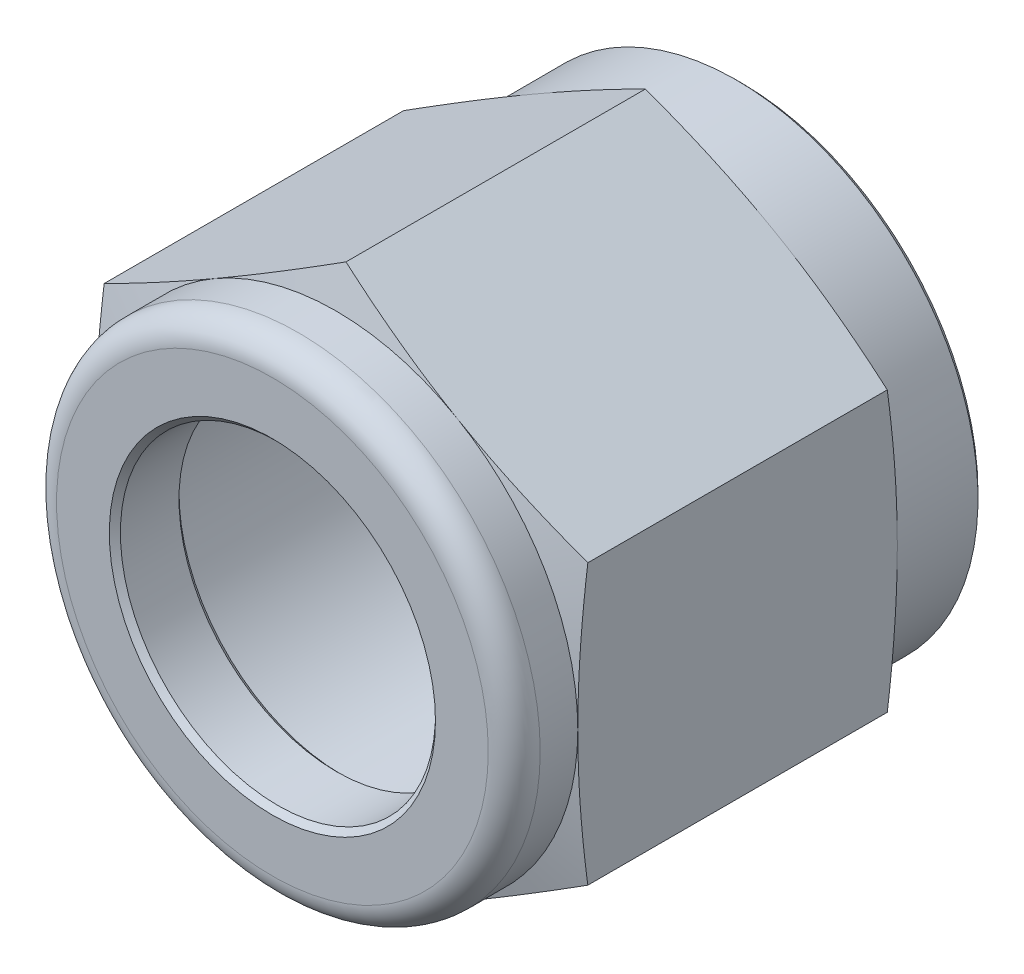
SolidWorks part; units mm, degrees
material "2024 Alloy"
ref_plane "Front Plane" through (0, 0, 0) normal (0, 0, 1) x (1, 0, 0)
ref_plane "Top Plane" through (0, 0, 0) normal (0, 1, 0) x (1, 0, 0)
ref_plane "Right Plane" through (0, 0, 0) normal (1, 0, 0) x (0, 0, -1)
sketch "Sketch0" plane through (0, 0, 0) normal (1, 0, 0) x (0, 0, -1)
  line L0 (0, 0) -> (-21.5646, 0) construction
  line L4 (-21.5646, 11.1125) -> (-21.5646, -11.1125) construction
  line L5 (-21.5646, 11.1125) -> (-21.5646, -11.1125) construction
  line L6 (-21.5646, 7.239) -> (-21.5646, -7.239) construction
  line L7 (0, 9.525) -> (0, -9.525) construction
  line L8 (0, -9.525) -> (0, 9.525) construction
  line L9 (0, -9.525) -> (-1.5875, -9.525) construction
  point P16 (-18.3642, 0)
  point P20 (-16.4338, 0)
  point P22 (-12.2936, 0)
  point P34 (-3.9624, 0)
  point P35 (-18.6436, 0)
  dimension "P" = 22.225
  dimension "M" = 21.5646
  dimension "L" = 18.3642
  dimension "S" = 16.4338
  dimension "Q" = 12.2936
  dimension "A" = 14.478
  dimension "C" = 22.225
  dimension "T" = 19.05
  dimension "B" = 3.9624
  dimension "J" = 14.6812
  dimension "H" = 19.05
  dimension "Pitch" = 1.5875
sketch "Sketch1" plane through (0, 0, 0) normal (0, 0, 1) x (1, 0, 0)
  line L1 (0, 12.8316) -> (-11.1125, 6.4158)
  line L2 (-11.1125, 6.4158) -> (-11.1125, -6.4158)
  line L3 (-11.1125, -6.4158) -> (0, -12.8316)
  line L4 (0, -12.8316) -> (11.1125, -6.4158)
  line L5 (11.1125, -6.4158) -> (11.1125, 6.4158)
  line L6 (11.1125, 6.4158) -> (0, 12.8316)
  circle A0 centre (0, 0) radius 11.1125 construction
extrude "Boss-Extrude1" add sketch "Sketch1" along normal up to vertex (21.5646 mm away) up to point (0, 0, 21.5646)
sketch "Sketch2" plane through (0, 0, 0) normal (1, 0, 0) x (0, 0, -1)
  line L0 (-21.5646, 14.5507) -> (-21.5646, 11.1125)
  line L1 (-21.5646, 11.1125) -> (-18.6436, 11.1125)
  line L2 (-18.6436, 11.1125) -> (-18.183, 12.8316)
  line L3 (-21.5646, 12.8316) -> (0, 12.8316) construction
  line L4 (-18.183, 12.8316) -> (-4.423, 12.8316)
  line L5 (-4.423, 12.8316) -> (-3.9624, 11.1125)
  line L6 (-3.9624, 11.1125) -> (-18.6436, 11.1125) construction
  line L7 (-3.9624, 11.1125) -> (0, 11.1125)
  line L8 (0, 11.1125) -> (0, 14.5507)
  line L9 (-21.5646, 14.5507) -> (0, 14.5507)
  line L10 (-3.9624, 11.1125) -> (-3.9624, 0) construction
  line L11 (-18.6436, 11.1125) -> (-18.6436, 0) construction
  line L12 (-21.5646, 7.239) -> (-21.5646, 0)
  line L13 (-21.5646, 11.1125) -> (-21.5646, -11.1125) construction
  line L14 (-21.5646, 0) -> (0, 0)
  line L15 (0, 0) -> (0, 8.7517)
  line L16 (-18.3642, 7.239) -> (-18.3642, 0) construction
  line L17 (-18.3642, 7.239) -> (-18.3642, 8.4977)
  line L18 (-18.1102, 8.7517) -> (0, 8.7517)
  line L19 (-18.3642, 7.239) -> (-21.5646, 7.239)
  line L23 (-16.4338, 0) -> (-16.4338, 8.7517) construction
  arc A0 (-18.3642, 8.4977) -> (-18.1102, 8.7517) centre (-18.1102, 8.4977) cw
  dimension "D3" = 0.254
  dimension "D1" = 15
  dimension "D2" = 15
  dimension "D4" = 0.7733
revolve "Cut-Revolve1" cut sketch "Sketch2" angle 360 about L0
sketch "Sketch3" [suppressed] plane through (0, 0, 0) normal (0, 0, -1) x (-1, 0, 0)
  circle A0 centre (0, 0) radius 8.7517
  circle A1 centre (0, 0) radius 8.7517 construction
  point P3 (0, 8.7517)
fillet "Fillet1" radius 1.1938 1 edges at (11.1125, 0, 21.5646)
chamfer "Chamfer1" distance 0.254 angle 45 1 edges at (11.1125, 0, 0)
chamfer "Chamfer2" distance 0.254 angle 45 2 edges at (0, 7.239, 18.3642) (0, 7.239, 21.5646)
ref_axis "Centre Axis 1" through (0, 0, 25.2505) along (0, 0, -1)
curve "Helix/Spiral1" [suppressed] pitch 1.5875 height 18.0213 turns 11.352 parameters "Pitch"=1.5875
sketch "Sketch4" [suppressed] plane through (0, 0, 0) normal (1, 0, 0) x (0, 0, -1)
  line L0 (-0.248, 8.322) -> (1.3395, 8.322) construction
  line L1 (1.3395, 8.322) -> (0.5457, 9.6969) construction
  line L2 (0.5457, 9.6969) -> (-0.248, 8.322) construction
  line L3 (0.4465, 9.525) -> (0.6449, 9.525) construction
  line L4 (0.5457, 8.7517) -> (0.5457, 8.322) construction
  line L5 (0, 8.7517) -> (1.0914, 8.7517) construction
  line L6 (0.5457, 9.6969) -> (0.5457, 9.525) construction
  line L7 (0.4465, 9.525) -> (-0.124, 8.5369)
  line L8 (-0.124, 8.5369) -> (1.2154, 8.5369)
  line L9 (1.2154, 8.5369) -> (0.6449, 9.525)
  arc A0 (0.6449, 9.525) -> (0.4465, 9.525) centre (0.5457, 9.4677) ccw
  point P6 (0.5457, 8.5369)
  dimension "D1" = 1.5875
  dimension "D2" = 1.3748
  dimension "D4" = 0.4296
  dimension "D3" = 0.1719
  dimension "D5" = 0.7733
sweep "Cut-Sweep1" [suppressed] cut profiles "Sketch4" path "Helix/Spiral1"
sketch "Sketch5" [suppressed] plane through (0, 0, 0) normal (0, 0, -1) x (-1, 0, 0)
  circle A0 centre (0, 0) radius 9.525
extrude "Cut-Extrude1" [suppressed] cut sketch "Sketch5" against normal through all draft 45
sketch "Sketch6" [suppressed] plane through (0, 0, 0) normal (1, 0, 0) x (0, 0, -1)
  line L0 (-18.3642, 9.6969) -> (-12.2936, 9.6969)
  line L1 (-12.2936, 9.6969) -> (-16.4338, 8.7517)
  line L2 (-16.4338, 8.7517) -> (-18.3642, 8.7517)
  line L3 (-18.3642, 8.7517) -> (-18.3642, 9.6969)
  line L4 (-12.2936, 0) -> (-12.2936, 9.6969) construction
  line L5 (-16.4338, 0) -> (-16.4338, 8.7517) construction
  line L7 (-18.3642, 8.7517) -> (-18.3642, 0) construction
  line L8 (-18.1102, 8.7517) -> (0, 8.7517) construction
  line L9 (-12.2936, 9.6969) -> (0.5457, 9.6969) construction
revolve "Revolve1" [suppressed] add sketch "Sketch6" angle 360 about L0
sketch "SketchX" [suppressed] plane through (0, 0, 0) normal (0, 0, -1) x (-1, 0, 0)
  line L0 (0, 0) -> (-4.7625, 8.2489) construction
  line L1 (-5.5562, 9.6237) -> (-11.1125, 6.4158) construction
  circle A0 centre (0, 0) radius 9.525 construction
equation "\"D3@Helix/Spiral1\"= \"Pitch@Sketch0\" + \"S@Sketch0\""
equation "\"D1@Sketch4\"=\"Pitch@Sketch0\""
equation "\"Pitch@Helix/Spiral1\"=\"Pitch@Sketch0\""
